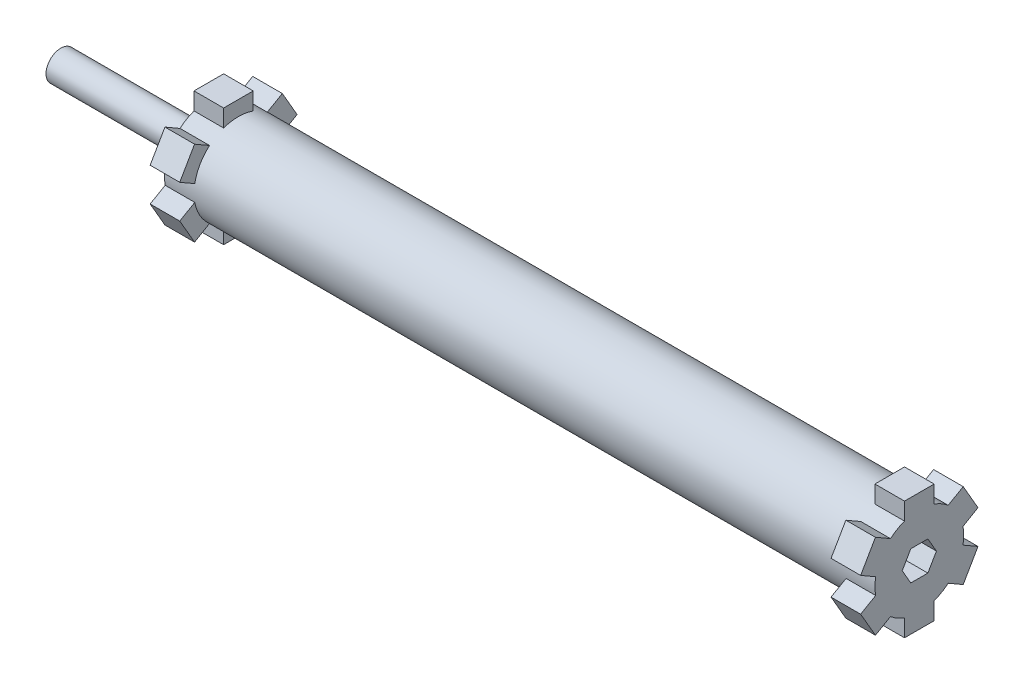
SolidWorks part; units mm, degrees
ref_plane "Plano frontal" through (0, 0, 0) normal (0, 0, 1) x (1, 0, 0)
ref_plane "Plano superior" through (0, 0, 0) normal (0, 1, 0) x (1, 0, 0)
ref_plane "Plano direito" through (0, 0, 0) normal (1, 0, 0) x (0, 0, -1)
sketch "Esboço1" plane through (0, 0, 0) normal (1, 0, 0) x (0, 0, -1)
  circle A0 centre (0, 0) radius 3
  dimension "D1" = 6
extrude "Ressalto-extrusão1" add sketch "Esboço1" along normal blind 48
sketch "Esboço2" plane through (0, 0, 0) normal (0, 1, 0) x (1, 0, 0)
  line L1 (2, -1) -> (-2, -1)
  line L2 (2, -1) -> (2, 1)
  line L3 (2, 1) -> (-2, 1)
  line L4 (-2, -1) -> (-2, 1)
  line L5 (2, -1) -> (-2, 1) construction
  line L6 (2, 1) -> (-2, -1) construction
  point P0 (0, 0)
  dimension "D1" = 2
  dimension "D2" = 4
extrude "Ressalto-extrusão2" add sketch "Esboço2" along normal blind 4 and the other way blind 4
sketch "Esboço4" plane through (-2, 0, 0) normal (-1, 0, 0) x (0, 0, 1)
  circle A0 centre (0, 0) radius 4.4712
extrude "Corte-extrusão2" cut sketch "Esboço4" against normal up to surface (2 mm away) up to face at (0, 0, 2)
sketch "Esboço5" plane through (0, 0, 0) normal (-1, 0, 0) x (0, 0, 1)
  circle A0 centre (0, 0) radius 3 construction
pattern_circular "PadrãoCircular1" count 6 over 360 about axis through (0, 0, 0) along (-1, 0, 0) of "Ressalto-extrusão2"
sketch "Esboço7" plane through (-2, 0, 0) normal (-1, 0, 0) x (0, 0, 1)
  circle A0 centre (0, 0) radius 7.7251
extrude "Corte-extrusão3" cut sketch "Esboço7" against normal up to surface (2 mm away) up to face at (0, 2.2948, 1.3249)
ref_plane "Plano3" through (24, 0, 0) normal (1, 0, 0) x (0, 0, -1)
mirror "Espelhar5" about plane through (24, 0, 0) normal (1, 0, 0) of "Ressalto-extrusão1", "Ressalto-extrusão2", "PadrãoCircular1"
sketch "Esboço10" plane through (50, 0, 0) normal (1, 0, 0) x (0, 0, -1)
  circle A0 centre (0, 0) radius 7.1809
extrude "Corte-extrusão5" cut sketch "Esboço10" against normal up to surface (2 mm away) up to face at (48, 2.2948, -1.3249)
sketch "Esboço11" plane through (0, 0, 0) normal (-1, 0, 0) x (0, 0, 1)
  circle A0 centre (0, 0) radius 1
  dimension "D1" = 2
extrude "Ressalto-extrusão3" add sketch "Esboço11" along normal blind 10
sketch "Esboço12" plane through (48, 0, 0) normal (1, 0, 0) x (0, 0, -1)
  line L1 (-0.5774, 1) -> (-1.1547, 0)
  line L2 (-1.1547, 0) -> (-0.5774, -1)
  line L3 (-0.5774, -1) -> (0.5774, -1)
  line L4 (0.5774, -1) -> (1.1547, 0)
  line L5 (1.1547, 0) -> (0.5774, 1)
  line L6 (0.5774, 1) -> (-0.5774, 1)
  circle A0 centre (0, 0) radius 1 construction
  dimension "D1" = 2
extrude "Corte-extrusão6" cut sketch "Esboço12" against normal blind 3
